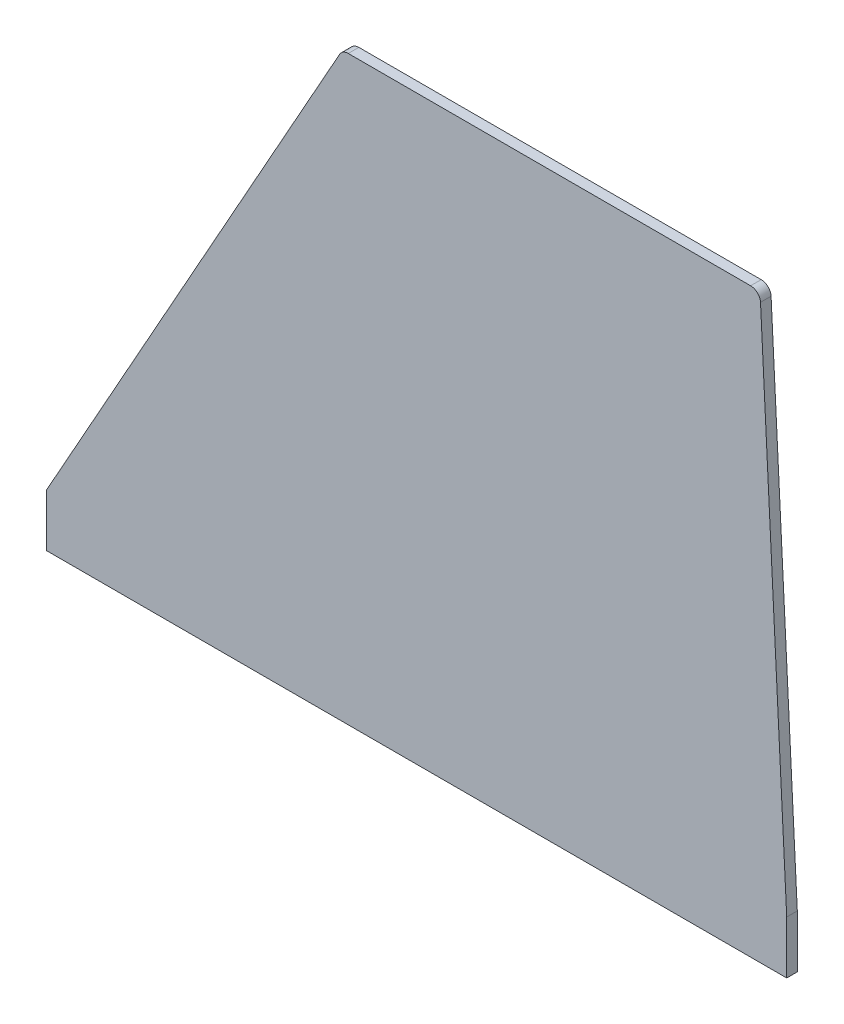
SolidWorks part; units mm, degrees
material "E-Glass Fiber"
ref_plane "Front Plane" through (0, 0, 0) normal (0, 0, 1) x (1, 0, 0)
ref_plane "Top Plane" through (0, 0, 0) normal (0, 1, 0) x (1, 0, 0)
ref_plane "Right Plane" through (0, 0, 0) normal (1, 0, 0) x (0, 0, -1)
sketch "Trapezoidal Fin Profile" plane through (0, 0, 0) normal (0, 0, 1) x (1, 0, 0)
  line L0 (381, -25.4) -> (0, -25.4)
  line L1 (0, -25.4) -> (0, 0)
  line L2 (0, 0) -> (156.7688, 152.4)
  line L3 (156.7688, 152.4) -> (359.9688, 152.4)
  line L5 (359.9688, 152.4) -> (381, 0)
  line L6 (381, 0) -> (381, -25.4)
  dimension "D2" = 381
  dimension "D3" = 203.2
  dimension "D4" = 156.7688
  dimension "D5" = 152.4
extrude "Trapezoidal Fin" [suppressed] add sketch "Trapezoidal Fin Profile" along normal blind 6.35 contours L2 L3 L5 L6 L0 L1
fillet "Trapezoidal Fin Fillets" [suppressed] radius 4.7625
sketch "Swept Fin Profile" [suppressed] plane through (0, 0, 0) normal (0, 0, 1) x (1, 0, 0)
  line L0 (0, 0) -> (267.9954, 0)
  line L1 (267.9954, 0) -> (398.268, 159.4104)
  line L2 (398.268, 159.4104) -> (264.2576, 159.4104)
  line L3 (264.2576, 159.4104) -> (0, 0)
  line L5 (52.0954, 0) -> (242.5954, 0)
  line L6 (52.0954, 0) -> (52.0954, -25.4)
  line L7 (52.0954, -25.4) -> (242.5954, -25.4)
  line L8 (242.5954, 0) -> (242.5954, -25.4)
  dimension "D1" = 267.9954
  dimension "D2" = 159.4104
  dimension "D3" = 134.0104
  dimension "D4" = 31.1
  dimension "D6" = 25.4
  dimension "D7" = 190.5
extrude "Boss-Extrude2" [suppressed] add sketch "Swept Fin Profile" along normal blind 6.35 contours L8 L0 L6 L7 | L0 L1 L2 L3
fillet "Fillet1" [suppressed] radius 4.7625
sketch "Sketch1" plane through (0, 0, 0) normal (0, 0, 1) x (1, 0, 0)
  line L0 (0, 0) -> (142.113, 254)
  line L1 (142.113, 254) -> (342.773, 254)
  line L2 (342.773, 254) -> (355.6, 0)
  line L3 (355.6, 0) -> (355.6, -25.4)
  line L4 (355.6, -25.4) -> (0, -25.4)
  line L5 (0, -25.4) -> (0, 0)
  point P6 (355.6, 22.6704)
  dimension "D1" = 355.6
  dimension "D2" = 200.66
  dimension "D3" = 25.4
  dimension "D4" = 142.113
  dimension "D5" = 25.4
  dimension "D6" = 254
extrude "Boss-Extrude3" add sketch "Sketch1" along normal mid plane 5.08
fillet "Fillet2" radius 4.7625 2 edges at (342.773, 254, 0) (142.113, 254, 0)
equation "\"Root Chord\"= 15"
equation "\"Span\"= 6"
equation "\"Tip Chord\"= 8"
equation "\"Sweep Distance\"= 6.1720"
equation "\"Fin Thickness\"= 0.25"
equation "\"Tab Height\"= 1"
equation "\"D1@Trapezoidal Fin Profile\" = \"Tab Height\""
equation "\"D2@Trapezoidal Fin Profile\" = \"Root Chord\""
equation "\"D3@Trapezoidal Fin Profile\" = \"Tip Chord\""
equation "\"D4@Trapezoidal Fin Profile\" = \"Sweep Distance\""
equation "\"D5@Trapezoidal Fin Profile\" = \"Span\""
equation "\"Fillet Radius\"=0.1875"
equation "\"D1@Trapezoidal Fin Fillets\"=\"Fillet Radius\""
equation "\"D1@Swept Fin Profile\" = 10.551"
equation "\"D4@Swept Fin Profile\" = 90 - 58.9"
